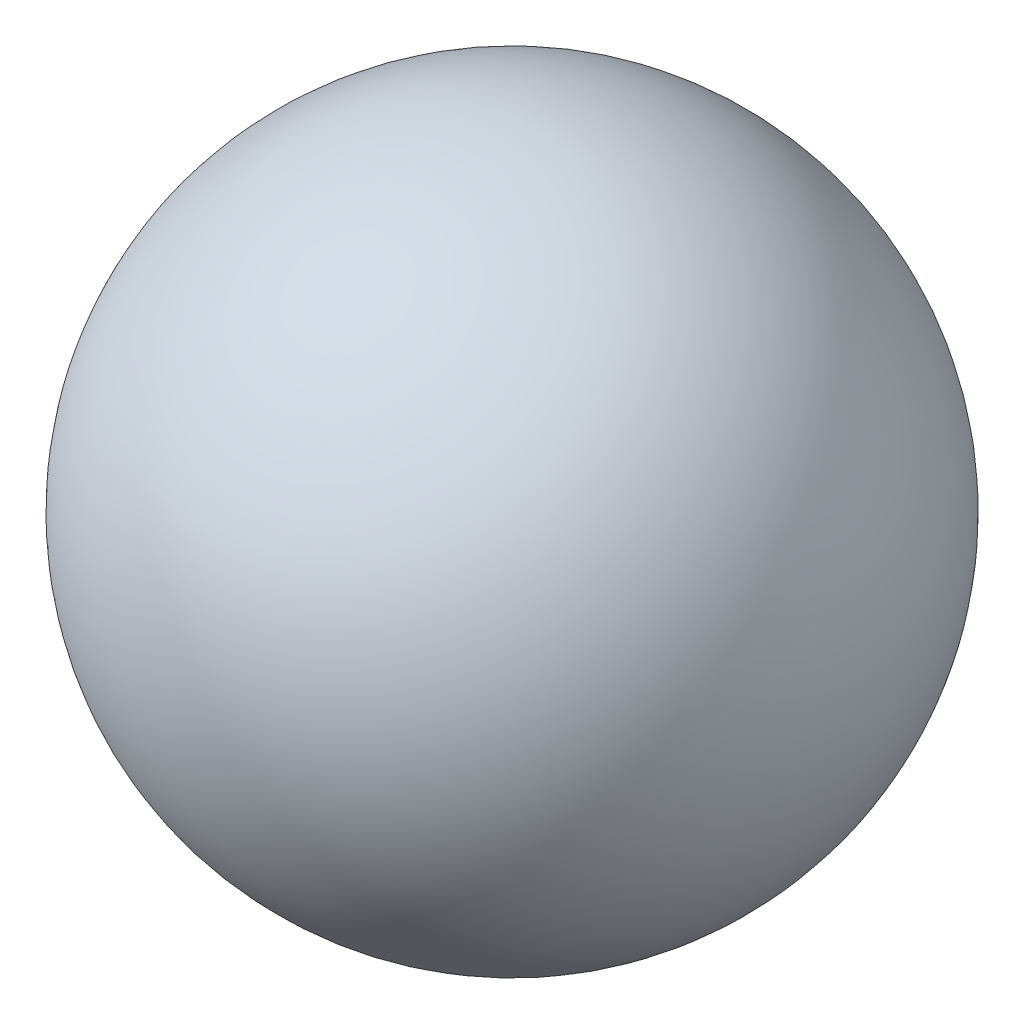
SolidWorks part; units mm, degrees
material "Tungsten Carbide"
ref_plane "Front" through (0, 0, 0) normal (0, 0, 1) x (1, 0, 0)
ref_plane "Top" through (0, 0, 0) normal (0, 1, 0) x (1, 0, 0)
ref_plane "Right" through (0, 0, 0) normal (1, 0, 0) x (0, 0, -1)
sketch "Sketch1" plane through (0, 0, 0) normal (0, 0, 1) x (1, 0, 0)
  line L0 (0, 0) -> (2.0179, 0) construction
  line L1 (0, 0) -> (-1.8828, 0) construction
  line L2 (-2.3813, 0) -> (2.3813, 0)
  arc A0 (2.3813, 0) -> (-2.3813, 0) centre (0, 0) ccw
  dimension "D1" = 4.7625
revolve "Revolve1" add sketch "Sketch1" angle 360 about L1
ref_axis "Axis1" through (-2.3813, 0, 0) along (1, 0, 0)
